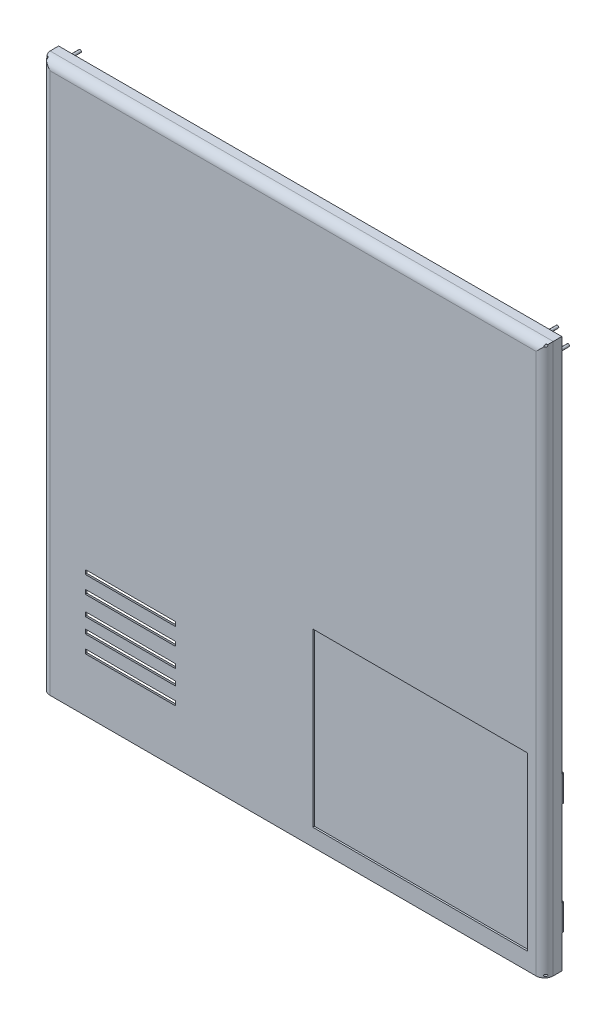
SolidWorks part; units mm, degrees
note: The reader was unsure of these and kept them because the rebuilt part matched: shared geometry of "Sketch6<3>".
ref_plane "Front Plane" through (0, 0, 0) normal (0, 0, 1) x (1, 0, 0)
ref_plane "Top Plane" through (0, 0, 0) normal (0, 1, 0) x (1, 0, 0)
ref_plane "Right Plane" through (0, 0, 0) normal (1, 0, 0) x (0, 0, -1)
sketch "Sketch1" plane through (0, 0, 0) normal (0, 0, 1) x (1, 0, 0)
  line L0 (-293, -320) -> (-293, 320)
  line L1 (288, -315) -> (-288, -315)
  line L2 (288, -315) -> (288, 315)
  line L3 (288, 315) -> (-288, 315)
  line L4 (-288, -315) -> (-288, 315)
  line L5 (288, -315) -> (-288, 315) construction
  line L6 (288, 315) -> (-288, -315) construction
  line L7 (293, 320) -> (-293, 320)
  line L8 (293, -320) -> (293, 320)
  line L9 (293, -320) -> (-293, -320)
  point P0 (0, 0)
  dimension "D1" = 630
  dimension "D2" = 576
  dimension "D3" = 5
extrude "Boss-Extrude1" add sketch "Sketch1" against normal blind 20 contours L4 L1 L2 L3 | L9 L8 L7 L0 L1 L4 L3 L2
fillet "Fillet1" radius 10 3 edges at (293, 0, 0) (-293, 0, 0) (0, 320, 0)
shell "Shell1" thickness 5
sketch "Sketch2" plane through (0, 0, -20) normal (0, 0, -1) x (-1, 0, 0)
  line L0 (-290.5, 317.5) -> (-290.5, -317.5) construction
  line L5 (-290.5, -317.5) -> (290.5, -317.5)
  line L6 (290.5, -317.5) -> (290.5, 317.5)
  line L7 (290.5, 317.5) -> (-290.5, 317.5) construction
  line L8 (-293, -320) -> (293, -320)
  line L9 (293, -320) -> (293, 320)
  line L10 (293, 320) -> (-293, 320)
  line L11 (-293, 320) -> (-293, -320)
  line L12 (-293, -320) -> (293, -320)
  line L13 (293, -320) -> (293, 320)
  line L14 (293, 320) -> (-293, 320) construction
  line L15 (-293, 320) -> (-293, -320) construction
  line L16 (0, 320) -> (0, -320) construction
  line L17 (293, 320) -> (293, -320) construction
  line L18 (290.5, 317.5) -> (290.5, -317.5) construction
  circle A0 centre (-290.5, 305) radius 1.5
  circle A1 centre (-290.5, -305) radius 1.5
  circle A2 centre (-278, 317.5) radius 1.5
  circle A3 centre (278, 317.5) radius 1.5
  circle A4 centre (290.5, -305) radius 1.5
  circle A5 centre (290.5, 305) radius 1.5
  dimension "D3" = 3
  dimension "D4" = 15
  dimension "D5" = 15
  dimension "D6" = 15
  dimension "D1" = 0
  dimension "D2" = 2.5
extrude "Boss-Extrude2" add sketch "Sketch2" along normal blind 10 contours A0 | A2 | A1 | A5 L6 | A3 | A4
sketch "Sketch3" plane through (0, 0, 0) normal (0, 0, 1) x (1, 0, 0)
  line L1 (-290.5, 317.5) -> (290.5, 317.5)
  line L2 (-290.5, 317.5) -> (-290.5, -320)
  line L3 (-290.5, -320) -> (290.5, -320)
  line L4 (290.5, 317.5) -> (290.5, -320)
  line L6 (-293, -320) -> (-283, -320) construction
  line L7 (-293, 320) -> (-283, 310) construction
  line L8 (-293, 320) -> (293, 320) construction
  line L9 (293, 320) -> (293, -320) construction
  point P0 (-290.5, 317.5)
  point P3 (290.5, 317.5)
  point P13 (290.5, -317.5)
  point P16 (-290.5, -317.5)
  dimension "D1" = 2.5
  dimension "D2" = 2.5
  dimension "D3" = 2.5
hole_wizard "CSK for M2 Countersunk Flat Head Screw1" positions "Sketch3" profile "Sketch4" countersink size "M2" standard "ISO"
sketch "Sketch4" plane through (-290.5, 317.5, 0) normal (1, 0, 0) x (0, -1, 0)
  line L0 (0, 0) -> (0, 30.721)
  line L1 (0, 30.721) -> (1.2, 30)
  line L2 (1.2, 30) -> (1.2, 1)
  line L3 (1.2, 1) -> (2.2, 0)
  line L5 (2.2, 0) -> (0, 0)
  line L6 (-1.2, 1) -> (-2.2, 0) construction
  line L10 (0, 30.721) -> (-1.2, 30) construction
  line L11 (0, -6.35) -> (0, 107.95) construction
  dimension "Hole Dia." = 2.4
  dimension "Hole Depth" = 30
  dimension "Near C'Sink Dia." = 4.4
  dimension "Near C'Sink Angle" = 90
  dimension "Drill Angle" = 118
sketch "Sketch5" plane through (0, 0, 0) normal (0, 0, 1) x (1, 0, 0)
  line L0 (283, -320) -> (-283, -320) construction
  line L1 (23, -100) -> (273, -100)
  line L2 (23, -100) -> (23, -300)
  line L3 (23, -300) -> (273, -300)
  line L4 (273, -100) -> (273, -300)
  line L5 (23, -100) -> (273, -300) construction
  line L6 (23, -300) -> (273, -100) construction
  line L7 (293, 320) -> (293, -320) construction
  point P0 (148, -200)
  dimension "D1" = 20
  dimension "D2" = 20
  dimension "D3" = 250
  dimension "D4" = 200
extrude "Cut-Extrude1" cut sketch "Sketch5" against normal blind 10
ref_plane "Plane1" through (0, 0, -2.5) normal (0, 0, 1) x (1, 0, 0)
sketch "Sketch6" plane through (0, 0, -2.5) normal (0, 0, 1) x (1, 0, 0)
  line L4 (273, -300) -> (273, -100) construction
  line L5 (23, -300) -> (273, -300) construction
  line L6 (273, -100) -> (23, -100) construction
  line L7 (23, -100) -> (23, -300) construction
  line L8 (-273, -310) -> (273, -310)
  line L9 (273, -310) -> (273, 300)
  line L10 (273, 300) -> (-273, 300)
  line L11 (-273, 300) -> (-273, -310)
  line L12 (-273, -310) -> (273, -310)
  line L13 (273, -310) -> (273, 300)
  line L14 (273, 300) -> (-273, 300)
  line L15 (-273, 300) -> (-273, -310)
  line L16 (273, -300) -> (273, -100)
  line L17 (23, -300) -> (273, -300)
  line L18 (273, -100) -> (23, -100)
  line L19 (23, -100) -> (23, -300)
  line L20 (275, -98) -> (21, -98)
  line L21 (21, -98) -> (21, -302)
  line L22 (21, -302) -> (275, -302)
  line L23 (275, -302) -> (275, -98)
  dimension "D1" = 10
  dimension "D2" = 2
extrude "Cut-Extrude2" cut sketch "Sketch6" against normal mid plane 1 contours L21 L22 L13 L17 L19 L18 L20
extrude "Boss-Extrude3" add sketch "Sketch6<3>" along normal mid plane 1 contours L18 L19 L17 L13 | L21 L22 L13 L17 L19 L18 L20
sketch "Sketch6<3>" plane through (0, 0, -2.5) normal (0, 0, 1) x (1, 0, 0) same geometry as "Sketch6"
sketch "Sketch7" plane through (0, 0, -20) normal (0, 0, -1) x (-1, 0, 0)
  circle A0 centre (-289.5, -305) radius 1.5
  dimension "D1" = 3
extrude "Cut-Extrude3" cut sketch "Sketch7" along normal blind 10
ref_plane "Plane2" through (290.5, 0, 0) normal (-1, 0, 0) x (0, 0, 1)
sketch "Sketch8" plane through (290.5, 0, 0) normal (-1, 0, 0) x (0, 0, 1)
  line L0 (-20, -90) -> (0, -90) construction
  line L1 (-20, -320) -> (-20, 320) construction
  line L2 (0, -320) -> (0, 310) construction
  line L3 (-20, 320) -> (-10, 320) construction
  line L4 (-20, -122.5) -> (-24, -122.5)
  line L5 (-24, -122.5) -> (-24, -152.5)
  line L6 (-24, -152.5) -> (-20, -152.5)
  line L7 (-20, -152.5) -> (-20, -122.5)
  line L8 (-20, -320) -> (-10, -320) construction
  line L9 (-20, -282.5) -> (-24, -282.5)
  line L10 (-20, -282.5) -> (-20, -252.5)
  line L11 (-20, -252.5) -> (-24, -252.5)
  line L12 (-24, -282.5) -> (-24, -252.5)
  dimension "D1" = 410
  dimension "D2" = 32.5
  dimension "D3" = 30
  dimension "D4" = 4
  dimension "D5" = 30
  dimension "D6" = 37.5
  dimension "D7" = 4
extrude "Boss-Extrude4" add sketch "Sketch8" along normal mid plane 5
sketch "Sketch9" plane through (0, -122.5, 0) normal (0, 1, 0) x (1, 0, 0)
  line L0 (293, 22) -> (288, 22) construction
  line L1 (293, 20) -> (293, 24) construction
  line L2 (288, 20) -> (288, 24) construction
  line L3 (289, 22) -> (288, 22)
  line L4 (292, 22) -> (293, 22)
  circle A0 centre (290.5, 22) radius 1.5
  dimension "D1" = 3
extrude "Cut-Extrude5" cut sketch "Sketch9" against normal blind 178 contours A0 L0 | L0 A0
sketch "Sketch10" plane through (0, -122.5, 0) normal (0, 1, 0) x (1, 0, 0)
  line L0 (288.75, 22) -> (288.75, 20)
  line L2 (293, 20) -> (-293, 20) construction
  line L4 (292.25, 22) -> (292.25, 20)
  circle A0 centre (290.5, 22) radius 1.75
  dimension "D1" = 3.5
extrude "Cut-Extrude6" cut sketch "Sketch10" against normal blind 178
sketch "Sketch11" plane through (0, 0, -30) normal (0, 0, -1) x (-1, 0, 0)
  circle A0 centre (-290.5, -305) radius 1.5
extrude "Cut-Extrude7" cut sketch "Sketch11" against normal up to surface (10 mm away) up to face at (290.5, -267.5, -20)
sketch "Sketch12" plane through (0, 0, 0) normal (0, 0, 1) x (1, 0, 0)
  line L0 (-242, -177.5) -> (-137, -177.5)
  line L1 (-242, -165) -> (-137, -165) construction
  line L2 (-242, -165) -> (-242, -270) construction
  line L3 (-242, -270) -> (-137, -270) construction
  line L4 (-137, -165) -> (-137, -270) construction
  line L5 (-242, -217.5) -> (-137, -217.5) construction
  line L6 (-242, -237.5) -> (-137, -237.5)
  line L7 (-242, -257.5) -> (-137, -257.5)
  line L8 (-242, -197.5) -> (-137, -197.5)
  line L10 (-242, -257.5) -> (-242, -252.5)
  line L11 (-242, -252.5) -> (-137, -252.5)
  line L12 (-137, -252.5) -> (-137, -257.5)
  line L13 (-242, -237.5) -> (-242, -232.5)
  line L14 (-242, -232.5) -> (-137, -232.5)
  line L15 (-137, -232.5) -> (-137, -237.5)
  line L16 (-242, -197.5) -> (-242, -192.5)
  line L17 (-242, -192.5) -> (-137, -192.5)
  line L18 (-137, -192.5) -> (-137, -197.5)
  line L19 (-242, -177.5) -> (-242, -172.5)
  line L20 (-242, -172.5) -> (-137, -172.5)
  line L21 (-137, -172.5) -> (-137, -177.5)
  line L22 (-242, -215) -> (-242, -220)
  line L23 (-242, -220) -> (-137, -220)
  line L24 (-137, -220) -> (-137, -215)
  line L25 (-137, -215) -> (-242, -215)
  line L26 (-242, -270) -> (-242, -165) construction
  dimension "D1" = 20
  dimension "D2" = 20
  dimension "D3" = 20
  dimension "D4" = 5
  dimension "D5" = 5
  dimension "D6" = 5
  dimension "D7" = 5
  dimension "D8" = 5
extrude "Cut-Extrude8" cut sketch "Sketch12" against normal blind 10 draft 30
